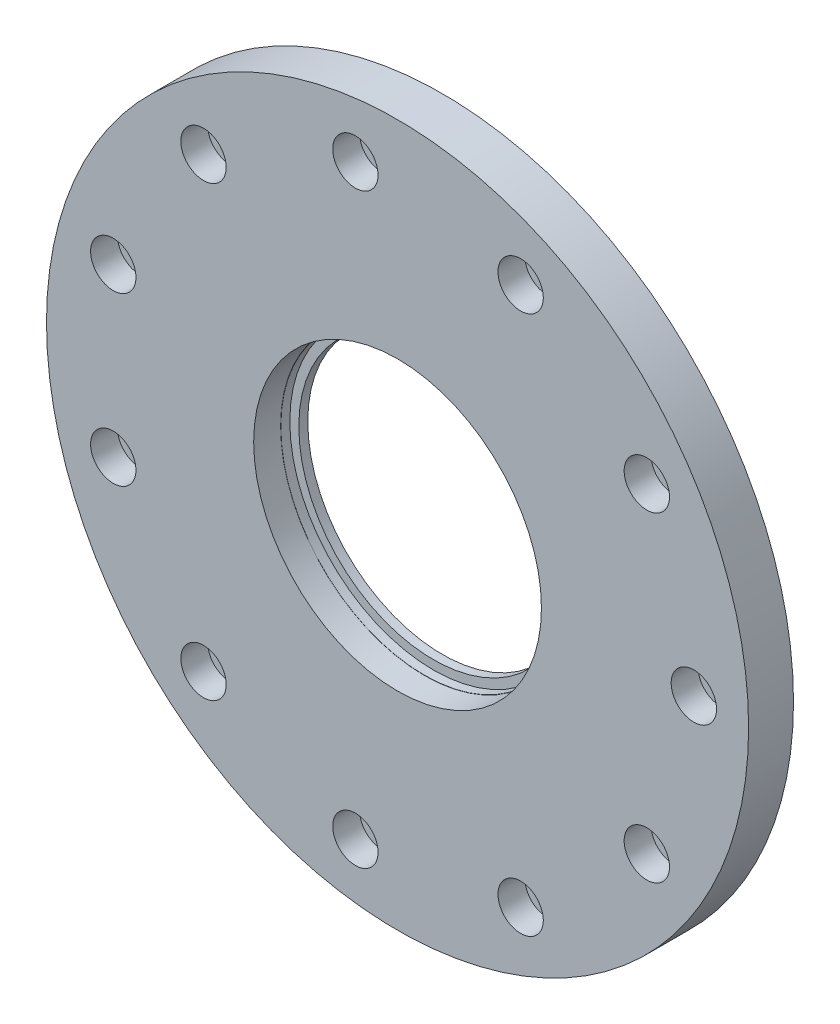
SolidWorks part; units mm, degrees
ref_plane "Front Plane" through (0, 0, 0) normal (0, 0, 1) x (1, 0, 0)
ref_plane "Top Plane" through (0, 0, 0) normal (0, 1, 0) x (1, 0, 0)
ref_plane "Right Plane" through (0, 0, 0) normal (1, 0, 0) x (0, 0, -1)
sketch "Sketch1" plane through (0, 0, 0) normal (0, 0, 1) x (1, 0, 0)
  circle A0 centre (0, 0) radius 39.1
  circle A1 centre (0, 0) radius 33 construction
  circle A2 centre (33, 0) radius 2.525
  circle A3 centre (27.7614, -17.8411) radius 2.525
  circle A4 centre (13.7087, -30.0179) radius 2.525
  circle A5 centre (-4.6964, -32.6641) radius 2.525
  circle A6 centre (-21.6104, -24.9397) radius 2.525
  circle A7 centre (-31.6633, -9.2972) radius 2.525
  circle A8 centre (-31.6633, 9.2972) radius 2.525
  circle A9 centre (-21.6104, 24.9397) radius 2.525
  circle A10 centre (-4.6964, 32.6641) radius 2.525
  circle A11 centre (13.7087, 30.0179) radius 2.525
  circle A12 centre (27.7614, 17.8411) radius 2.525
  circle A13 centre (0, 0) radius 16.025
  point P28 (0, 0)
extrude "Boss-Extrude1" add sketch "Sketch1" along normal blind 3
sketch "Sketch2" plane through (0, 0, 0) normal (0, 0, -1) x (-1, 0, 0)
  circle A0 centre (0, 0) radius 16
  circle A1 centre (0, 0) radius 39.1
  circle A2 centre (0, 0) radius 39.1 construction
  dimension "D1" = 32
extrude "Boss-Extrude2" add sketch "Sketch2" along normal blind 2 contours A1 | A0
sketch "Sketch3" plane through (0, 0, 3) normal (0, 0, 1) x (1, 0, 0)
  circle A0 centre (33, 0) radius 1.6
  circle A1 centre (27.7614, -17.8411) radius 1.6
  circle A2 centre (13.7087, -30.0179) radius 1.6
  circle A3 centre (-4.6964, -32.6641) radius 1.6
  circle A4 centre (-21.6104, -24.9397) radius 1.6
  circle A5 centre (-31.6633, -9.2972) radius 1.6
  circle A6 centre (-31.6633, 9.2972) radius 1.6
  circle A7 centre (-21.6104, 24.9397) radius 1.6
  circle A8 centre (-4.6964, 32.6641) radius 1.6
  circle A9 centre (13.7087, 30.0179) radius 1.6
  circle A10 centre (27.7614, 17.8411) radius 1.6
  point P25 (0, 0)
  dimension "D1" = 3.2
  dimension "D2" = 11
extrude "Cut-Extrude1" cut sketch "Sketch3" against normal through all
sketch "Sketch4" plane through (0, 0, -2) normal (0, 0, -1) x (-1, 0, 0)
  circle A0 centre (0, 0) radius 16
  circle A1 centre (0, 0) radius 15
  dimension "D1" = 32
  dimension "D2" = 30
extrude "Boss-Extrude3" add sketch "Sketch4" against normal blind 1
